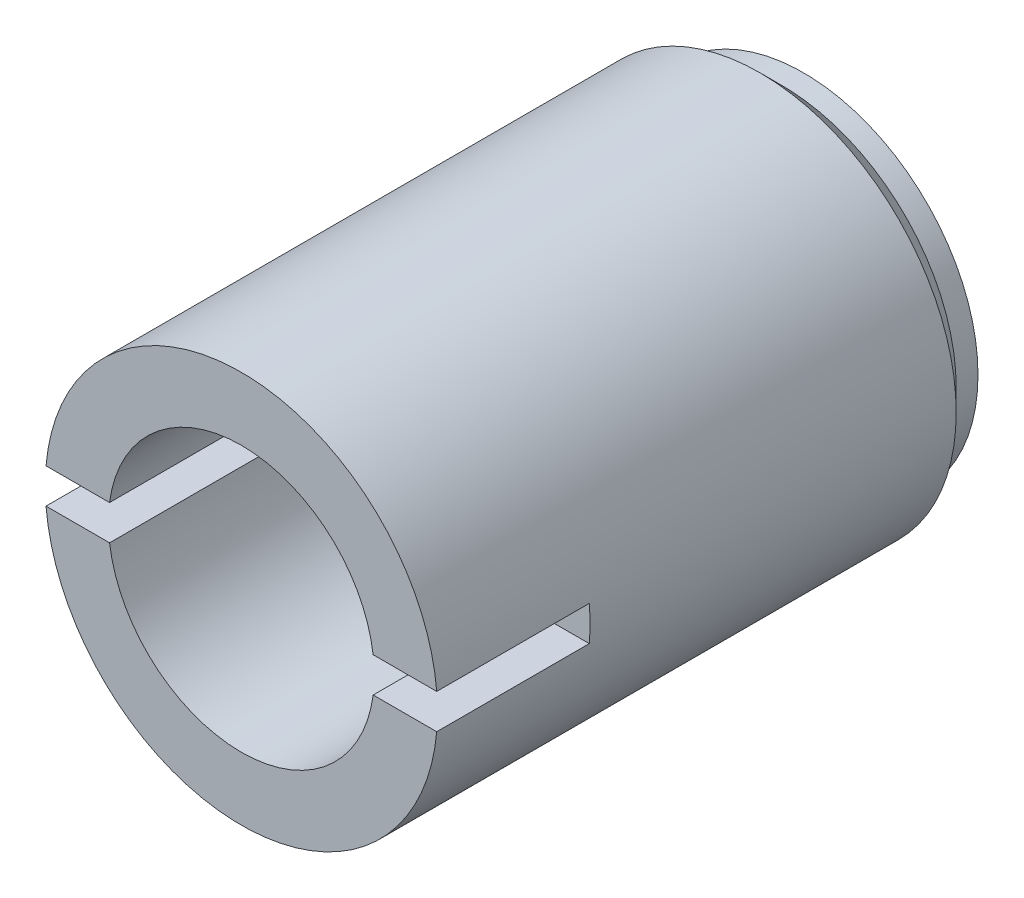
SolidWorks part; units mm, degrees
ref_plane "Front Plane" through (0, 0, 0) normal (1, 0, 0) x (0, 1, 0)
ref_plane "Top Plane" through (0, 0, 0) normal (0, 0, 1) x (0, 1, 0)
ref_plane "Right Plane" through (0, 0, 0) normal (0, 1, 0) x (-1, 0, 0)
sketch "Sketch1" plane through (0, 0, 0) normal (0, 0, 1) x (0, 1, 0)
  circle A0 centre (0, 0) radius 2.75
  circle A1 centre (0, 0) radius 1.6
  dimension "D1" = 5.5
  dimension "D2" = 3.2
extrude "Boss-Extrude1" add sketch "Sketch1" along normal blind 0.5
sketch "Sketch2" plane through (0, 0, 0.5) normal (0, 0, 1) x (1, 0, 0)
  circle A0 centre (0, 0) radius 1.6
  circle A1 centre (0, 0) radius 1.6 construction
  circle A2 centre (0, 0) radius 4.5
  dimension "D1" = 9
extrude "Boss-Extrude2" add sketch "Sketch2" along normal blind 7.4
chamfer "Chamfer1" distance 0.5 angle 45 1 edges at (4.5, 0, 0.5)
sketch "Sketch3" plane through (0, 0, 7.9) normal (0, 0, 1) x (1, 0, 0)
  circle A0 centre (0, 0) radius 2.5
  circle A1 centre (0, 0) radius 4.5
  circle A2 centre (0, 0) radius 4.5 construction
  dimension "D1" = 5
extrude "Boss-Extrude3" add sketch "Sketch3" along normal blind 2.2
sketch "Sketch4" plane through (0, 0, 10.1) normal (0, 0, 1) x (1, 0, 0)
  circle A0 centre (0, 0) radius 4.5
  circle A1 centre (0, 0) radius 4.5 construction
  circle A2 centre (0, 0) radius 3.05
  dimension "D1" = 6.1
extrude "Boss-Extrude4" add sketch "Sketch4" along normal blind 2.8
sketch "Sketch5" plane through (0, 0, 0) normal (1, 0, 0) x (0, 1, 0)
  line L0 (3.05, 12.9) -> (-3.05, 12.9) construction
  line L1 (-0.4, 12.9) -> (0.4, 12.9)
  line L2 (-0.4, 12.9) -> (-0.4, 9.4)
  line L3 (-0.4, 9.4) -> (0.4, 9.4)
  line L4 (0.4, 12.9) -> (0.4, 9.4)
  point P6 (0, 12.9)
  dimension "D1" = 3.5
  dimension "D2" = 0.8
extrude "Cut-Extrude1" cut sketch "Sketch5" against normal mid plane 9
sketch "Sketch6" plane through (0, 0, 0) normal (0, 0, -1) x (1, 0, 0)
  circle A0 centre (0, 0) radius 2.75
  circle A1 centre (0, 0) radius 4
  circle A2 centre (0, 0) radius 4 construction
  circle A3 centre (0, 0) radius 2.75 construction
extrude "Boss-Extrude6" add sketch "Sketch6" against normal up to surface (0.5 mm away) up to face at (4, 0, 0.5)
sketch "Sketch7" plane through (0, 0, 10.1) normal (0, 0, 1) x (1, 0, 0)
  circle A0 centre (0, 0) radius 3.05
  arc A2 (3.0237, 0.4) -> (-3.0237, 0.4) centre (0, 0) ccw construction
extrude "Cut-Extrude2" cut sketch "Sketch7" against normal up to surface (2.2 mm away) up to face at (1.6, 0, 7.9)
